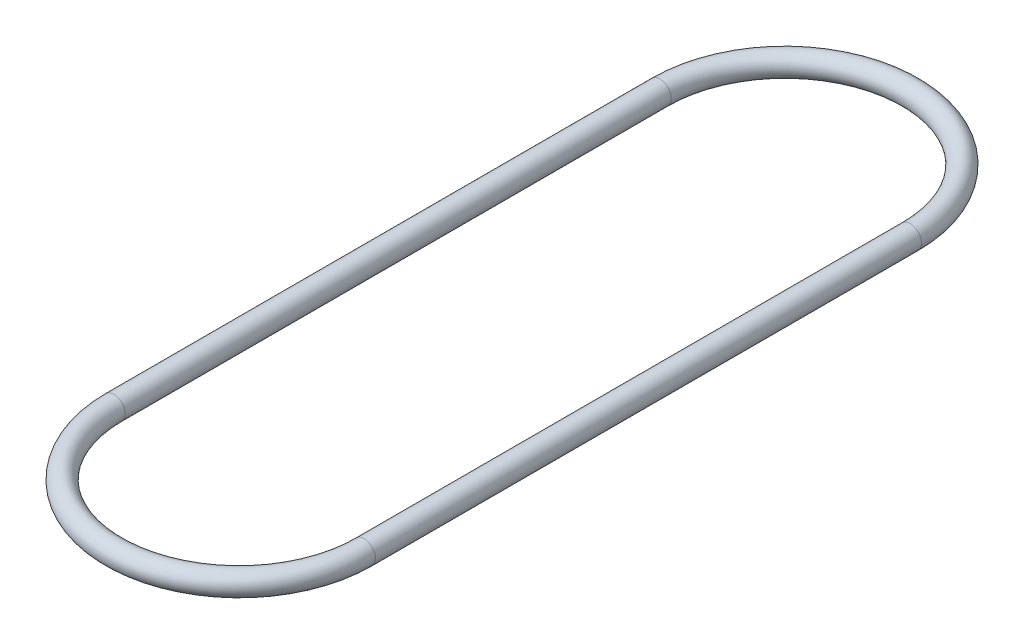
SolidWorks part; units mm, degrees
ref_plane "Front" through (0, 0, 0) normal (0, 0, 1) x (1, 0, 0)
ref_plane "Top" through (0, 0, 0) normal (0, 1, 0) x (1, 0, 0)
ref_plane "Right" through (0, 0, 0) normal (1, 0, 0) x (0, 0, -1)
sketch "Sketch1" plane through (0, 0, 0) normal (0, 0, 1) x (1, 0, 0)
  circle A0 centre (0, 0) radius 3.175
  dimension "D1" = 6.35
sketch "Sketch2" plane through (0, 0, 0) normal (0, 1, 0) x (1, 0, 0)
  line L0 (34.925, 0) -> (34.925, 152.4) construction
  line L1 (0, 0) -> (0, 152.4)
  line L2 (69.85, 0) -> (69.85, 152.4)
  arc A0 (0, 0) -> (69.85, 0) centre (34.925, 0) ccw
  arc A1 (69.85, 152.4) -> (0, 152.4) centre (34.925, 152.4) ccw
  point P2 (34.925, 76.2)
  dimension "D1" = 69.85
  dimension "D2" = 152.4
sweep "Sweep1" add profiles "Sketch1" path "Sketch2"
ref_axis "Axis1" through (34.925, 0, -152.4) along (0, 1, 0)
ref_axis "Axis2" through (34.925, 0, 0) along (0, 1, 0)
